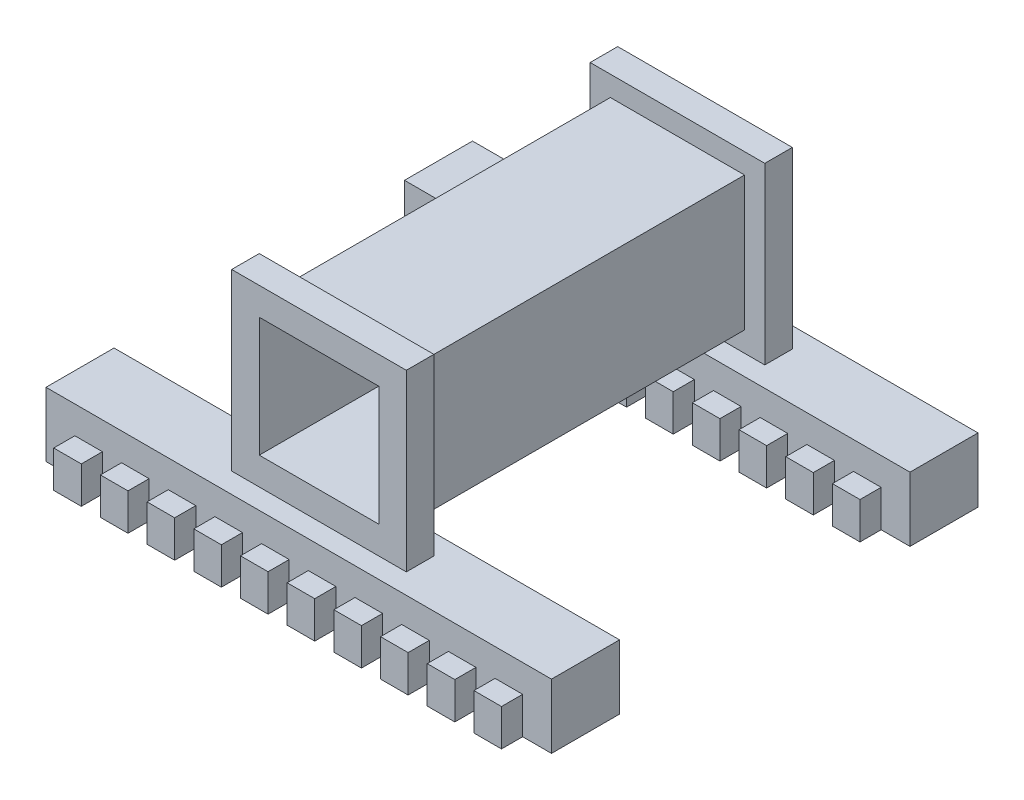
SolidWorks part; units mm, degrees
ref_plane "前视基准面" through (0, 0, 0) normal (0, 0, 1) x (1, 0, 0)
ref_plane "上视基准面" through (0, 0, 0) normal (0, 1, 0) x (1, 0, 0)
ref_plane "右视基准面" through (0, 0, 0) normal (1, 0, 0) x (0, 0, -1)
sketch "草图1" plane through (0, 0, 0) normal (0, 0, 1) x (1, 0, 0)
  line L0 (-9.5, 9.5) -> (9.5, 9.5)
  line L1 (-6.5, -6.5) -> (6.5, -6.5)
  line L2 (-6.5, -6.5) -> (-6.5, 6.5)
  line L3 (-6.5, 6.5) -> (6.5, 6.5)
  line L4 (6.5, -6.5) -> (6.5, 6.5)
  line L5 (-6.5, -6.5) -> (6.5, 6.5) construction
  line L6 (-6.5, 6.5) -> (6.5, -6.5) construction
  line L7 (9.5, -9.5) -> (9.5, 9.5)
  line L8 (-9.5, -9.5) -> (9.5, -9.5)
  line L9 (-9.5, -9.5) -> (-9.5, 9.5)
  line L10 (-7.3, 7.3) -> (7.3, 7.3)
  line L11 (7.3, -7.3) -> (7.3, 7.3)
  line L12 (-7.3, -7.3) -> (7.3, -7.3)
  line L13 (-7.3, -7.3) -> (-7.3, 7.3)
  line L15 (-27.5, -9.5) -> (27.5, -9.5)
  line L16 (-27.5, -9.5) -> (-27.5, -16.5)
  line L17 (-27.5, -16.5) -> (27.5, -16.5)
  line L18 (27.5, -9.5) -> (27.5, -16.5)
  point P0 (0, 0)
  dimension "D1" = 3
  dimension "D2" = 0.8
extrude "凸台-拉伸1" add sketch "草图1" along normal mid plane 42 contours L18 L15 L8 L16 L17 | L9 L8 L7 L0 L12 L13 L10 L11 | L13 L10 L11 L12 region at (0, 9.2313, 0) region at (0, -13, 0)
extrude "切除-拉伸1" cut sketch "草图1<3>" against normal mid plane 42 contours L2 L3 L4 L1
sketch "草图1<3>" plane through (0, 0, 0) normal (0, 0, 1) x (1, 0, 0) same geometry as "草图1"
sketch "草图2" plane through (0, 0, 0) normal (1, 0, 0) x (0, 0, -1)
  line L0 (21, -16.5) -> (21, -9.5) construction
  line L1 (21, -9.5) -> (-21, -9.5) construction
  line L2 (-21, -9.5) -> (-21, -16.5) construction
  line L3 (-21, -16.5) -> (21, -16.5) construction
  line L4 (21, -9.5) -> (21, 9.5) construction
  line L5 (21, 9.5) -> (-21, 9.5) construction
  line L6 (-21, 9.5) -> (-21, -9.5) construction
  line L7 (-21, -9.5) -> (21, -9.5) construction
  line L8 (21, -16.5) -> (21, -9.5)
  line L9 (21, -9.5) -> (-21, -9.5)
  line L10 (-21, -9.5) -> (-21, -16.5)
  line L11 (-21, -16.5) -> (21, -16.5)
  line L12 (21, -9.5) -> (21, 9.5)
  line L13 (21, 9.5) -> (-21, 9.5)
  line L14 (-21, 9.5) -> (-21, -9.5)
  line L15 (-21, -9.5) -> (21, -9.5)
extrude "切除-拉伸6" cut sketch "草图1<12>" against normal mid plane 36 contours L1 L4 L3 L2 | L9 L0 L7 L8 | L13 L10 L11 L12 region at (0, 0, 0)
sketch "草图1<12>" plane through (0, 0, 0) normal (0, 0, 1) x (1, 0, 0) same geometry as "草图1"
extrude "切除-拉伸7" cut sketch "草图1<13>" against normal mid plane 29 contours L18 L15 L8 L16 L17 region at (0, -13, 0)
sketch "草图1<13>" plane through (0, 0, 0) normal (0, 0, 1) x (1, 0, 0) same geometry as "草图1"
sketch "草图4" plane through (0, 0, 0) normal (1, 0, 0) x (0, 0, -1)
  line L0 (-21, -9.5) -> (-14.5, -9.5) construction
  line L1 (-14.5, -9.5) -> (-14.5, -16.5) construction
  line L2 (-14.5, -16.5) -> (-21, -16.5) construction
  line L3 (-21, -16.5) -> (-21, -9.5) construction
  line L4 (-18, 9.5) -> (-18, -9.5) construction
  line L5 (-18, -9.5) -> (-21, -9.5) construction
  line L6 (-21, -9.5) -> (-21, 9.5) construction
  line L7 (-21, 9.5) -> (-18, 9.5) construction
  line L8 (-18, -7.3) -> (-18, 7.3) construction
  line L9 (-18, 7.3) -> (18, 7.3) construction
  line L10 (18, 7.3) -> (18, -7.3) construction
  line L11 (18, -7.3) -> (-18, -7.3) construction
  line L12 (21, -9.5) -> (18, -9.5) construction
  line L13 (18, -9.5) -> (18, 9.5) construction
  line L14 (18, 9.5) -> (21, 9.5) construction
  line L15 (21, 9.5) -> (21, -9.5) construction
  line L16 (14.5, -16.5) -> (14.5, -9.5) construction
  line L17 (14.5, -9.5) -> (21, -9.5) construction
  line L18 (21, -9.5) -> (21, -16.5) construction
  line L19 (21, -16.5) -> (14.5, -16.5) construction
  line L20 (-21, -9.5) -> (-14.5, -9.5)
  line L21 (-14.5, -9.5) -> (-14.5, -16.5)
  line L22 (-14.5, -16.5) -> (-21, -16.5)
  line L23 (-21, -16.5) -> (-21, -9.5)
  line L24 (-18, 9.5) -> (-18, -9.5)
  line L25 (-18, -9.5) -> (-21, -9.5)
  line L26 (-21, -9.5) -> (-21, 9.5)
  line L27 (-21, 9.5) -> (-18, 9.5)
  line L28 (-18, -7.3) -> (-18, 7.3)
  line L29 (-18, 7.3) -> (18, 7.3)
  line L30 (18, 7.3) -> (18, -7.3)
  line L31 (18, -7.3) -> (-18, -7.3)
  line L32 (21, -9.5) -> (18, -9.5)
  line L33 (18, -9.5) -> (18, 9.5)
  line L34 (18, 9.5) -> (21, 9.5)
  line L35 (21, 9.5) -> (21, -9.5)
  line L36 (14.5, -16.5) -> (14.5, -9.5)
  line L37 (14.5, -9.5) -> (21, -9.5)
  line L38 (21, -9.5) -> (21, -16.5)
  line L39 (21, -16.5) -> (14.5, -16.5)
  line L40 (21, -9.5) -> (24.5, -9.5)
  line L41 (24.5, -9.5) -> (24.5, -16.5)
  line L42 (24.5, -16.5) -> (21, -16.5)
  line L43 (-21, -16.5) -> (-24.5049, -16.5)
  line L44 (-24.5049, -16.5) -> (-24.5049, -9.5)
  line L45 (-24.5049, -9.5) -> (-21, -9.5)
extrude "凸台-拉伸2" add sketch "草图4" along normal mid plane 55 contours L42 L41 L40 L38 | L45 L44 L43 L23 region at (0, -13, 22.7525) region at (0, -13, -22.75)
sketch "草图5" plane through (0, 0, -24.5) normal (0, 0, -1) x (-1, 0, 0)
  line L4 (27.5, -16.5) -> (27.5, -9.5)
  line L5 (27.5, -9.5) -> (-27.5, -9.5)
  line L6 (-27.5, -9.5) -> (-27.5, -16.5)
  line L7 (-27.5, -16.5) -> (27.5, -16.5)
  line L8 (27.5, -16.5) -> (27.5, -9.5)
  line L9 (27.5, -9.5) -> (-27.5, -9.5)
  line L10 (-27.5, -9.5) -> (-27.5, -16.5)
  line L12 (-9.5, -9.5) -> (9.5, -9.5)
  line L13 (-9.5, 9.5) -> (-9.5, -9.5)
  line L14 (9.5, 9.5) -> (-9.5, 9.5)
  line L15 (9.5, -9.5) -> (9.5, 9.5)
  line L16 (-9.5, -9.5) -> (9.5, -9.5)
  line L17 (-9.5, 9.5) -> (-9.5, -9.5)
  line L18 (9.5, 9.5) -> (-9.5, 9.5)
  line L19 (9.5, -9.5) -> (9.5, 9.5)
  line L24 (-27.5, -16.5) -> (27.5, -16.5) construction
  line L37 (22.8593, -16.5) -> (27.5, -16.5)
  line L50 (-21.36, -16.5) -> (-24.36, -16.5)
  line L55 (-11.187, -12.5036) -> (-14.213, -12.5036)
  line L56 (-11.187, -12.5036) -> (-11.187, -16.5)
  line L61 (-6.12, -16.5) -> (-9.12, -16.5)
  line L62 (-6.12, -16.5) -> (-6.12, -12.5036)
  line L68 (-1.04, -16.4978) -> (-4.04, -16.4978)
  line L86 (9.12, -16.5) -> (6.12, -16.5)
  line L91 (9.12, -16.5) -> (9.12, -12.5)
  line L92 (9.12, -12.5) -> (6.12, -12.5)
  line L97 (6.12, -16.5) -> (6.12, -12.5)
  line L98 (9.12, -16.5) -> (6.12, -12.5) construction
  line L103 (-21.36, -16.5) -> (-21.36, -12.5036)
  line L104 (-21.36, -12.5036) -> (-24.36, -12.5036)
  line L105 (-24.36, -16.5) -> (-24.36, -12.5036)
  line L106 (-21.36, -16.5) -> (-24.36, -12.5036) construction
  line L107 (-21.36, -12.5036) -> (-24.36, -16.5) construction
  line L108 (-19.28, -16.5) -> (-16.28, -16.5)
  line L109 (-19.28, -16.5) -> (-19.28, -12.5036)
  line L110 (-19.28, -12.5036) -> (-16.28, -12.5036)
  line L111 (-16.28, -16.5) -> (-16.28, -12.5036)
  line L112 (-19.28, -16.5) -> (-16.28, -12.5036) construction
  line L113 (-19.28, -12.5036) -> (-16.28, -16.5) construction
  line L114 (-11.187, -16.5) -> (-14.213, -16.5)
  line L115 (-14.213, -12.5036) -> (-14.213, -16.5)
  line L116 (-11.187, -12.5036) -> (-14.213, -16.5) construction
  line L117 (-11.187, -16.5) -> (-14.213, -12.5036) construction
  line L118 (-6.12, -12.5036) -> (-9.12, -12.5036)
  line L119 (-9.12, -16.5) -> (-9.12, -12.5036)
  line L120 (-6.12, -16.5) -> (-9.12, -12.5036) construction
  line L121 (-6.12, -12.5036) -> (-9.12, -16.5) construction
  line L122 (-1.04, -16.4978) -> (-1.04, -12.4978)
  line L123 (-1.04, -12.4978) -> (-4.04, -12.4978)
  line L124 (-4.04, -16.4978) -> (-4.04, -12.4978)
  line L125 (-1.04, -16.4978) -> (-4.04, -12.4978) construction
  line L126 (-1.04, -12.4978) -> (-4.04, -16.4978) construction
  line L128 (9.12, -12.5) -> (6.12, -16.5) construction
  line L129 (4.04, -16.5) -> (1.038, -16.5)
  line L130 (4.04, -16.5) -> (4.04, -12.4956)
  line L131 (4.04, -12.4956) -> (1.038, -12.4956)
  line L132 (1.038, -16.5) -> (1.038, -12.4956)
  line L133 (4.04, -16.5) -> (1.038, -12.4956) construction
  line L134 (4.04, -12.4956) -> (1.038, -16.5) construction
  line L135 (14.2014, -16.5) -> (11.1986, -16.5)
  line L136 (14.2014, -16.5) -> (14.2014, -12.5)
  line L137 (14.2014, -12.5) -> (11.1986, -12.5)
  line L138 (11.1986, -16.5) -> (11.1986, -12.5)
  line L139 (14.2014, -16.5) -> (11.1986, -12.5) construction
  line L140 (14.2014, -12.5) -> (11.1986, -16.5) construction
  line L141 (19.28, -16.4935) -> (16.28, -16.4935)
  line L142 (19.28, -16.4935) -> (19.28, -12.4935)
  line L143 (19.28, -12.4935) -> (16.28, -12.4935)
  line L144 (16.28, -16.4935) -> (16.28, -12.4935)
  line L145 (19.28, -16.4935) -> (16.28, -12.4935) construction
  line L146 (19.28, -12.4935) -> (16.28, -16.4935) construction
  line L151 (24.3586, -16.5) -> (21.36, -16.5)
  line L152 (24.3586, -16.5) -> (24.3586, -12.487)
  line L153 (24.3586, -12.487) -> (21.36, -12.487)
  line L154 (21.36, -16.5) -> (21.36, -12.487)
  line L155 (24.3586, -16.5) -> (21.36, -12.487) construction
  line L156 (24.3586, -12.487) -> (21.36, -16.5) construction
  point P6 (-22.86, -14.5018)
  point P11 (0, 0)
  point P33 (-17.78, -14.5018)
  point P35 (-17.78, -14.5018)
  point P39 (-12.7, -14.5018)
  point P40 (-12.7, -14.5018)
  point P45 (-7.62, -14.5018)
  point P50 (-2.54, -14.4978)
  point P55 (2.539, -14.4978)
  point P60 (7.62, -14.5)
  point P65 (12.7, -14.5)
  point P70 (17.78, -14.4935)
  point P75 (22.8593, -14.4935)
  dimension "D1" = 0
  dimension "D2" = 0
sketch "草图10" plane through (27.5, 0, 0) normal (1, 0, 0) x (0, 0, -1)
  line L0 (-24.5049, -16.5) -> (-25.5049, -16.5)
  line L1 (-24.5049, -16.5) -> (-24.5049, -9.5)
  line L2 (-24.5049, -9.5) -> (-25.5049, -9.5)
  line L3 (-25.5049, -9.5) -> (-25.5049, -16.5)
  line L4 (-14.5, -16.5) -> (-13.5, -16.5)
  line L5 (-13.5, -16.5) -> (-13.5, -9.5)
  line L6 (-13.5, -9.5) -> (-14.5, -9.5)
  line L7 (-14.5, -9.5) -> (-14.5, -16.5)
  line L8 (14.4975, -9.5) -> (14.4975, -16.5)
  line L11 (-0.0012, -16.5) -> (-0.0012, -9.5)
  line L12 (13.4975, -9.5) -> (14.4975, -9.5)
  line L13 (13.4975, -16.5) -> (13.4975, -9.5)
  line L14 (14.4975, -16.5) -> (13.4975, -16.5)
  line L15 (25.5025, -9.5) -> (25.5025, -16.5)
  line L16 (24.5025, -9.5) -> (25.5025, -9.5)
  line L17 (24.5025, -16.5) -> (24.5025, -9.5)
  line L18 (24.5025, -16.5) -> (25.5025, -16.5)
extrude "凸台-拉伸4" add sketch "草图10" against normal blind 55 contours L7 L4 L5 L6 | L3 L0 L1 L2
sketch "草图14" plane through (27.5, 0, 0) normal (1, 0, 0) x (0, 0, -1)
  line L0 (14.5, -9.5) -> (13.5, -9.5)
  line L1 (14.5, -16.5) -> (13.5, -16.5)
  line L2 (13.5, -16.5) -> (13.5, -9.5)
  line L3 (24.5, -9.5) -> (25.5, -9.5)
  line L4 (24.5, -16.5) -> (25.5, -16.5)
  line L5 (25.5, -16.5) -> (25.5, -9.5)
  line L6 (24.5, -9.5) -> (24.5, -16.5)
  line L7 (14.5, -9.5) -> (14.5, -16.5)
extrude "凸台-拉伸6" add sketch "草图14" against normal blind 55
sketch "草图15" plane through (0, 0, -25.5) normal (0, 0, -1) x (-1, 0, 0)
  line L0 (-27.5, -16.5) -> (-22.86, -16.5)
  line L1 (27.5, -16.5) -> (-27.5, -16.5) construction
  line L2 (-22.86, -16.5) -> (-22.86, -12.5)
  line L4 (-17.78, -12.5) -> (-17.78, -16.5)
  line L5 (-11.2, -16.5) -> (-14.2, -16.5)
  line L6 (-12.7, -16.5) -> (-12.7, -12.5)
  line L7 (-11.2, -16.5) -> (-11.2, -12.5)
  line L8 (-7.62, -12.5) -> (-7.62, -16.5)
  line L9 (-11.2, -12.5) -> (-14.2, -12.5)
  line L10 (-2.54, -16.5) -> (-2.54, -12.5)
  line L11 (-1.04, -16.5) -> (-4.04, -16.5)
  line L12 (2.54, -12.5) -> (2.54, -16.5)
  line L13 (-1.04, -16.5) -> (-1.04, -12.5)
  line L14 (7.62, -16.5) -> (7.62, -12.5)
  line L15 (6.12, -16.5) -> (9.12, -16.5)
  line L16 (12.7, -12.5) -> (12.7, -16.5)
  line L17 (6.12, -16.5) -> (6.12, -12.5)
  line L18 (17.78, -16.5) -> (17.78, -12.5)
  line L19 (6.12, -12.5) -> (9.12, -12.5)
  line L20 (22.86, -12.5) -> (22.86, -16.5)
  line L21 (24.36, -16.5) -> (21.36, -16.5)
  line L31 (24.36, -16.5) -> (24.36, -12.5)
  line L32 (24.36, -12.5) -> (21.36, -12.5)
  line L37 (9.12, -16.5) -> (9.12, -12.5)
  line L38 (6.12, -16.5) -> (9.12, -12.5) construction
  line L39 (-19.28, -16.5) -> (-16.28, -16.5)
  line L48 (-21.36, -16.5) -> (-24.36, -16.5)
  line L49 (-21.36, -16.5) -> (-21.36, -12.5)
  line L50 (-21.36, -12.5) -> (-24.36, -12.5)
  line L51 (-24.36, -16.5) -> (-24.36, -12.5)
  line L52 (-21.36, -16.5) -> (-24.36, -12.5) construction
  line L53 (-21.36, -12.5) -> (-24.36, -16.5) construction
  line L58 (-19.28, -16.5) -> (-19.28, -12.5)
  line L59 (-19.28, -12.5) -> (-16.28, -12.5)
  line L60 (-16.28, -16.5) -> (-16.28, -12.5)
  line L61 (-19.28, -16.5) -> (-16.28, -12.5) construction
  line L62 (-19.28, -12.5) -> (-16.28, -16.5) construction
  line L67 (-14.2, -16.5) -> (-14.2, -12.5)
  line L68 (-11.2, -16.5) -> (-14.2, -12.5) construction
  line L69 (-11.2, -12.5) -> (-14.2, -16.5) construction
  line L70 (-9.12, -16.5) -> (-6.12, -16.5)
  line L71 (-9.12, -16.5) -> (-9.12, -12.5)
  line L72 (-9.12, -12.5) -> (-6.12, -12.5)
  line L73 (-6.12, -16.5) -> (-6.12, -12.5)
  line L74 (-9.12, -16.5) -> (-6.12, -12.5) construction
  line L75 (-9.12, -12.5) -> (-6.12, -16.5) construction
  line L76 (-1.04, -12.5) -> (-4.04, -12.5)
  line L77 (-4.04, -16.5) -> (-4.04, -12.5)
  line L78 (-1.04, -16.5) -> (-4.04, -12.5) construction
  line L79 (-1.04, -12.5) -> (-4.04, -16.5) construction
  line L80 (4.04, -16.5) -> (1.04, -16.5)
  line L81 (4.04, -16.5) -> (4.04, -12.5)
  line L82 (4.04, -12.5) -> (1.04, -12.5)
  line L83 (1.04, -16.5) -> (1.04, -12.5)
  line L84 (4.04, -16.5) -> (1.04, -12.5) construction
  line L85 (4.04, -12.5) -> (1.04, -16.5) construction
  line L86 (6.12, -12.5) -> (9.12, -16.5) construction
  line L87 (11.2, -16.5) -> (14.2, -16.5)
  line L88 (11.2, -16.5) -> (11.2, -12.5)
  line L89 (11.2, -12.5) -> (14.2, -12.5)
  line L90 (14.2, -16.5) -> (14.2, -12.5)
  line L91 (11.2, -16.5) -> (14.2, -12.5) construction
  line L92 (11.2, -12.5) -> (14.2, -16.5) construction
  line L93 (16.28, -16.5) -> (19.28, -16.5)
  line L94 (16.28, -16.5) -> (16.28, -12.5)
  line L95 (16.28, -12.5) -> (19.28, -12.5)
  line L96 (19.28, -16.5) -> (19.28, -12.5)
  line L97 (16.28, -16.5) -> (19.28, -12.5) construction
  line L98 (16.28, -12.5) -> (19.28, -16.5) construction
  line L99 (21.36, -16.5) -> (21.36, -12.5)
  line L100 (24.36, -16.5) -> (21.36, -12.5) construction
  line L101 (24.36, -12.5) -> (21.36, -16.5) construction
  point P17 (22.86, -14.5)
  point P25 (22.86, -14.5)
  point P26 (22.86, -14.5)
  point P31 (17.78, -14.5)
  point P32 (7.62, -14.5)
  point P36 (-22.86, -14.5)
  point P41 (-17.78, -14.5)
  point P42 (-17.78, -14.5)
  point P47 (-12.7, -14.5)
  point P52 (-7.62, -14.5)
  point P57 (-2.54, -14.5)
  point P62 (2.54, -14.5)
  point P68 (12.7, -14.5)
  point P73 (17.78, -14.5)
  point P78 (0, 0)
  point P79 (0, 0)
  line M64 (-27.5, -9.5) -> (-27.5, -16.5)
  line M65 (-27.5, -16.5) -> (27.5, -16.5)
  line M66 (27.5, -16.5) -> (27.5, -9.5)
  line M67 (27.5, -9.5) -> (-27.5, -9.5)
extrude "切除-拉伸17" cut sketch "草图15" against normal blind 2.3 contours L99 L32 L31 L51 L50 L49 L58 L59 L60 L67 L9 L7 L71 L72 L73 L77 L76 L13 L83 L82 L81 L17 L19 L37 L88 L89 L90 L94 M65 M66 M67 M64 region at (0, -12.3208, -25.5)
sketch "草图16" plane through (0, 0, 13.5) normal (0, 0, -1) x (-1, 0, 0)
  line L0 (21.36, -16.5) -> (24.36, -16.5) construction
  line L1 (24.36, -16.5) -> (24.36, -12.5) construction
  line L2 (24.36, -12.5) -> (21.36, -12.5) construction
  line L3 (21.36, -12.5) -> (21.36, -16.5) construction
  line L4 (-27.5, -9.5) -> (-27.5, -16.5)
  line L5 (-27.5, -16.5) -> (27.5, -16.5)
  line L6 (27.5, -16.5) -> (27.5, -9.5)
  line L7 (27.5, -9.5) -> (-27.5, -9.5)
  line L8 (-27.5, -9.5) -> (-27.5, -16.5)
  line L9 (-27.5, -16.5) -> (27.5, -16.5)
  line L10 (27.5, -16.5) -> (27.5, -9.5)
  line L11 (27.5, -9.5) -> (-27.5, -9.5)
  line L12 (16.28, -16.5) -> (19.28, -16.5) construction
  line L13 (19.28, -16.5) -> (19.28, -12.5) construction
  line L14 (19.28, -12.5) -> (16.28, -12.5) construction
  line L15 (16.28, -12.5) -> (16.28, -16.5) construction
  line L16 (11.2, -16.5) -> (14.2, -16.5) construction
  line L17 (14.2, -16.5) -> (14.2, -12.5) construction
  line L18 (14.2, -12.5) -> (11.2, -12.5) construction
  line L19 (11.2, -12.5) -> (11.2, -16.5) construction
  line L20 (6.12, -16.5) -> (9.12, -16.5) construction
  line L21 (9.12, -16.5) -> (9.12, -12.5) construction
  line L22 (9.12, -12.5) -> (6.12, -12.5) construction
  line L23 (6.12, -12.5) -> (6.12, -16.5) construction
  line L24 (1.04, -16.5) -> (4.04, -16.5) construction
  line L25 (4.04, -16.5) -> (4.04, -12.5) construction
  line L26 (4.04, -12.5) -> (1.04, -12.5) construction
  line L27 (1.04, -12.5) -> (1.04, -16.5) construction
  line L28 (-4.04, -16.5) -> (-1.04, -16.5) construction
  line L29 (-1.04, -16.5) -> (-1.04, -12.5) construction
  line L30 (-1.04, -12.5) -> (-4.04, -12.5) construction
  line L31 (-4.04, -12.5) -> (-4.04, -16.5) construction
  line L32 (-9.12, -16.5) -> (-6.12, -16.5) construction
  line L33 (-6.12, -16.5) -> (-6.12, -12.5) construction
  line L34 (-6.12, -12.5) -> (-9.12, -12.5) construction
  line L35 (-9.12, -12.5) -> (-9.12, -16.5) construction
  line L36 (-14.2, -16.5) -> (-11.2, -16.5) construction
  line L37 (-11.2, -16.5) -> (-11.2, -12.5) construction
  line L38 (-11.2, -12.5) -> (-14.2, -12.5) construction
  line L39 (-14.2, -12.5) -> (-14.2, -16.5) construction
  line L40 (-19.28, -16.5) -> (-16.28, -16.5) construction
  line L41 (-16.28, -16.5) -> (-16.28, -12.5) construction
  line L42 (-16.28, -12.5) -> (-19.28, -12.5) construction
  line L43 (-19.28, -12.5) -> (-19.28, -16.5) construction
  line L44 (-24.36, -16.5) -> (-21.36, -16.5) construction
  line L45 (-21.36, -16.5) -> (-21.36, -12.5) construction
  line L46 (-21.36, -12.5) -> (-24.36, -12.5) construction
  line L47 (-24.36, -12.5) -> (-24.36, -16.5) construction
  line L48 (21.36, -16.5) -> (24.36, -16.5)
  line L49 (24.36, -16.5) -> (24.36, -12.5)
  line L50 (24.36, -12.5) -> (21.36, -12.5)
  line L51 (21.36, -12.5) -> (21.36, -16.5)
  line L52 (16.28, -16.5) -> (19.28, -16.5)
  line L53 (19.28, -16.5) -> (19.28, -12.5)
  line L54 (19.28, -12.5) -> (16.28, -12.5)
  line L55 (16.28, -12.5) -> (16.28, -16.5)
  line L56 (11.2, -16.5) -> (14.2, -16.5)
  line L57 (14.2, -16.5) -> (14.2, -12.5)
  line L58 (14.2, -12.5) -> (11.2, -12.5)
  line L59 (11.2, -12.5) -> (11.2, -16.5)
  line L60 (6.12, -16.5) -> (9.12, -16.5)
  line L61 (9.12, -16.5) -> (9.12, -12.5)
  line L62 (9.12, -12.5) -> (6.12, -12.5)
  line L63 (6.12, -12.5) -> (6.12, -16.5)
  line L64 (1.04, -16.5) -> (4.04, -16.5)
  line L65 (4.04, -16.5) -> (4.04, -12.5)
  line L66 (4.04, -12.5) -> (1.04, -12.5)
  line L67 (1.04, -12.5) -> (1.04, -16.5)
  line L68 (-4.04, -16.5) -> (-1.04, -16.5)
  line L69 (-1.04, -16.5) -> (-1.04, -12.5)
  line L70 (-1.04, -12.5) -> (-4.04, -12.5)
  line L71 (-4.04, -12.5) -> (-4.04, -16.5)
  line L72 (-9.12, -16.5) -> (-6.12, -16.5)
  line L73 (-6.12, -16.5) -> (-6.12, -12.5)
  line L74 (-6.12, -12.5) -> (-9.12, -12.5)
  line L75 (-9.12, -12.5) -> (-9.12, -16.5)
  line L76 (-14.2, -16.5) -> (-11.2, -16.5)
  line L77 (-11.2, -16.5) -> (-11.2, -12.5)
  line L78 (-11.2, -12.5) -> (-14.2, -12.5)
  line L79 (-14.2, -12.5) -> (-14.2, -16.5)
  line L80 (-19.28, -16.5) -> (-16.28, -16.5)
  line L81 (-16.28, -16.5) -> (-16.28, -12.5)
  line L82 (-16.28, -12.5) -> (-19.28, -12.5)
  line L83 (-19.28, -12.5) -> (-19.28, -16.5)
  line L84 (-24.36, -16.5) -> (-21.36, -16.5)
  line L85 (-21.36, -16.5) -> (-21.36, -12.5)
  line L86 (-21.36, -12.5) -> (-24.36, -12.5)
  line L87 (-24.36, -12.5) -> (-24.36, -16.5)
  line M5 (-27.5, -9.5) -> (-27.5, -16.5)
  line M6 (-27.5, -16.5) -> (27.5, -16.5)
  line M7 (27.5, -16.5) -> (27.5, -9.5)
  line M8 (27.5, -9.5) -> (-27.5, -9.5)
  dimension "D1" = 0
extrude "切除-拉伸18" cut sketch "草图16" against normal blind 2.3 contours L87 L86 L85 L83 L82 L81 L79 L78 L77 L75 L74 L73 L71 L70 L69 L67 L66 L65 L63 L62 L61 L59 L58 L57 L55 L54 L53 L51 L50 L49 M6 M7 M8 M5 region at (0, -12.3208, 13.5)
sketch "草图17" plane through (0, 0, -13.5) normal (0, 0, 1) x (1, 0, 0)
  line L0 (-21.36, -16.5) -> (-24.36, -16.5) construction
  line L1 (-24.36, -16.5) -> (-24.36, -12.5) construction
  line L2 (-24.36, -12.5) -> (-21.36, -12.5) construction
  line L3 (-21.36, -12.5) -> (-21.36, -16.5) construction
  line L4 (27.5, -16.5) -> (27.5, -9.5)
  line L5 (27.5, -9.5) -> (-27.5, -9.5)
  line L6 (-27.5, -9.5) -> (-27.5, -16.5)
  line L7 (-27.5, -16.5) -> (27.5, -16.5)
  line L8 (27.5, -16.5) -> (27.5, -9.5)
  line L9 (27.5, -9.5) -> (-27.5, -9.5)
  line L10 (-27.5, -9.5) -> (-27.5, -16.5)
  line L11 (-27.5, -16.5) -> (27.5, -16.5)
  line L12 (-16.28, -16.5) -> (-19.28, -16.5) construction
  line L13 (-19.28, -16.5) -> (-19.28, -12.5) construction
  line L14 (-19.28, -12.5) -> (-16.28, -12.5) construction
  line L15 (-16.28, -12.5) -> (-16.28, -16.5) construction
  line L16 (-11.2, -16.5) -> (-14.2, -16.5) construction
  line L17 (-14.2, -16.5) -> (-14.2, -12.5) construction
  line L18 (-14.2, -12.5) -> (-11.2, -12.5) construction
  line L19 (-11.2, -12.5) -> (-11.2, -16.5) construction
  line L20 (-6.12, -16.5) -> (-9.12, -16.5) construction
  line L21 (-9.12, -16.5) -> (-9.12, -12.5) construction
  line L22 (-9.12, -12.5) -> (-6.12, -12.5) construction
  line L23 (-6.12, -12.5) -> (-6.12, -16.5) construction
  line L24 (-1.04, -16.5) -> (-4.04, -16.5) construction
  line L25 (-4.04, -16.5) -> (-4.04, -12.5) construction
  line L26 (-4.04, -12.5) -> (-1.04, -12.5) construction
  line L27 (-1.04, -12.5) -> (-1.04, -16.5) construction
  line L28 (4.04, -16.5) -> (1.04, -16.5) construction
  line L29 (1.04, -16.5) -> (1.04, -12.5) construction
  line L30 (1.04, -12.5) -> (4.04, -12.5) construction
  line L31 (4.04, -12.5) -> (4.04, -16.5) construction
  line L32 (9.12, -16.5) -> (6.12, -16.5) construction
  line L33 (6.12, -16.5) -> (6.12, -12.5) construction
  line L34 (6.12, -12.5) -> (9.12, -12.5) construction
  line L35 (9.12, -12.5) -> (9.12, -16.5) construction
  line L36 (14.2, -16.5) -> (11.2, -16.5) construction
  line L37 (11.2, -16.5) -> (11.2, -12.5) construction
  line L38 (11.2, -12.5) -> (14.2, -12.5) construction
  line L39 (14.2, -12.5) -> (14.2, -16.5) construction
  line L40 (19.28, -16.5) -> (16.28, -16.5) construction
  line L41 (16.28, -16.5) -> (16.28, -12.5) construction
  line L42 (16.28, -12.5) -> (19.28, -12.5) construction
  line L43 (19.28, -12.5) -> (19.28, -16.5) construction
  line L44 (21.36, -12.5) -> (24.36, -12.5) construction
  line L45 (24.36, -12.5) -> (24.36, -16.5) construction
  line L46 (24.36, -16.5) -> (21.36, -16.5) construction
  line L47 (21.36, -16.5) -> (21.36, -12.5) construction
  line L48 (-21.36, -16.5) -> (-24.36, -16.5)
  line L49 (-24.36, -16.5) -> (-24.36, -12.5)
  line L50 (-24.36, -12.5) -> (-21.36, -12.5)
  line L51 (-21.36, -12.5) -> (-21.36, -16.5)
  line L52 (-16.28, -16.5) -> (-19.28, -16.5)
  line L53 (-19.28, -16.5) -> (-19.28, -12.5)
  line L54 (-19.28, -12.5) -> (-16.28, -12.5)
  line L55 (-16.28, -12.5) -> (-16.28, -16.5)
  line L56 (-11.2, -16.5) -> (-14.2, -16.5)
  line L57 (-14.2, -16.5) -> (-14.2, -12.5)
  line L58 (-14.2, -12.5) -> (-11.2, -12.5)
  line L59 (-11.2, -12.5) -> (-11.2, -16.5)
  line L60 (-6.12, -16.5) -> (-9.12, -16.5)
  line L61 (-9.12, -16.5) -> (-9.12, -12.5)
  line L62 (-9.12, -12.5) -> (-6.12, -12.5)
  line L63 (-6.12, -12.5) -> (-6.12, -16.5)
  line L64 (-1.04, -16.5) -> (-4.04, -16.5)
  line L65 (-4.04, -16.5) -> (-4.04, -12.5)
  line L66 (-4.04, -12.5) -> (-1.04, -12.5)
  line L67 (-1.04, -12.5) -> (-1.04, -16.5)
  line L68 (4.04, -16.5) -> (1.04, -16.5)
  line L69 (1.04, -16.5) -> (1.04, -12.5)
  line L70 (1.04, -12.5) -> (4.04, -12.5)
  line L71 (4.04, -12.5) -> (4.04, -16.5)
  line L72 (9.12, -16.5) -> (6.12, -16.5)
  line L73 (6.12, -16.5) -> (6.12, -12.5)
  line L74 (6.12, -12.5) -> (9.12, -12.5)
  line L75 (9.12, -12.5) -> (9.12, -16.5)
  line L76 (14.2, -16.5) -> (11.2, -16.5)
  line L77 (11.2, -16.5) -> (11.2, -12.5)
  line L78 (11.2, -12.5) -> (14.2, -12.5)
  line L79 (14.2, -12.5) -> (14.2, -16.5)
  line L80 (19.28, -16.5) -> (16.28, -16.5)
  line L81 (16.28, -16.5) -> (16.28, -12.5)
  line L82 (16.28, -12.5) -> (19.28, -12.5)
  line L83 (19.28, -12.5) -> (19.28, -16.5)
  line L84 (21.36, -12.5) -> (24.36, -12.5)
  line L85 (24.36, -12.5) -> (24.36, -16.5)
  line L86 (24.36, -16.5) -> (21.36, -16.5)
  line L87 (21.36, -16.5) -> (21.36, -12.5)
  line M5 (27.5, -16.5) -> (27.5, -9.5)
  line M6 (27.5, -9.5) -> (-27.5, -9.5)
  line M7 (-27.5, -9.5) -> (-27.5, -16.5)
  line M8 (-27.5, -16.5) -> (27.5, -16.5)
  dimension "D1" = 0
extrude "切除-拉伸19" cut sketch "草图17" against normal blind 2.3 contours L87 L84 L85 L11 L49 L50 L51 L53 L54 L55 L57 L58 L59 L61 L62 L63 L65 L66 L67 L69 L70 L71 L73 L74 L75 L77 L78 L79 L81 L82 L83 M8 M5 M6 M7 region at (0, -12.3208, -13.5)
sketch "草图18" plane through (0, 0, 25.5049) normal (0, 0, 1) x (1, 0, 0)
  line L0 (24.36, -16.5) -> (24.36, -12.5) construction
  line L1 (24.36, -12.5) -> (21.36, -12.5) construction
  line L2 (21.36, -12.5) -> (21.36, -16.5) construction
  line L3 (21.36, -16.5) -> (24.36, -16.5) construction
  line L4 (27.5, -16.5) -> (27.5, -9.5)
  line L5 (27.5, -9.5) -> (-27.5, -9.5)
  line L6 (-27.5, -9.5) -> (-27.5, -16.5)
  line L7 (-27.5, -16.5) -> (27.5, -16.5)
  line L8 (27.5, -16.5) -> (27.5, -9.5)
  line L9 (27.5, -9.5) -> (-27.5, -9.5)
  line L10 (-27.5, -9.5) -> (-27.5, -16.5)
  line L11 (-27.5, -16.5) -> (27.5, -16.5)
  line L12 (-16.28, -16.5) -> (-16.28, -12.5)
  line L13 (-16.28, -12.5) -> (-19.28, -12.5)
  line L14 (-19.28, -12.5) -> (-19.28, -16.5)
  line L15 (-19.28, -16.5) -> (-16.28, -16.5)
  line L16 (-16.28, -16.5) -> (-16.28, -12.5)
  line L17 (-16.28, -12.5) -> (-19.28, -12.5)
  line L18 (-19.28, -12.5) -> (-19.28, -16.5)
  line L19 (-19.28, -16.5) -> (-16.28, -16.5)
  line L20 (19.28, -16.5) -> (19.28, -12.5) construction
  line L21 (19.28, -12.5) -> (16.28, -12.5) construction
  line L22 (16.28, -12.5) -> (16.28, -16.5) construction
  line L23 (16.28, -16.5) -> (19.28, -16.5) construction
  line L24 (14.2, -16.5) -> (14.2, -12.5) construction
  line L25 (14.2, -12.5) -> (11.2, -12.5) construction
  line L26 (11.2, -12.5) -> (11.2, -16.5) construction
  line L27 (11.2, -16.5) -> (14.2, -16.5) construction
  line L28 (9.12, -16.5) -> (9.12, -12.5) construction
  line L29 (9.12, -12.5) -> (6.12, -12.5) construction
  line L30 (6.12, -12.5) -> (6.12, -16.5) construction
  line L31 (6.12, -16.5) -> (9.12, -16.5) construction
  line L32 (4.04, -16.5) -> (4.04, -12.5) construction
  line L33 (4.04, -12.5) -> (1.04, -12.5) construction
  line L34 (1.04, -12.5) -> (1.04, -16.5) construction
  line L35 (1.04, -16.5) -> (4.04, -16.5) construction
  line L36 (-1.04, -16.5) -> (-1.04, -12.5) construction
  line L37 (-1.04, -12.5) -> (-4.04, -12.5) construction
  line L38 (-4.04, -12.5) -> (-4.04, -16.5) construction
  line L39 (-4.04, -16.5) -> (-1.04, -16.5) construction
  line L40 (-6.12, -16.5) -> (-6.12, -12.5) construction
  line L41 (-6.12, -12.5) -> (-9.12, -12.5) construction
  line L42 (-9.12, -12.5) -> (-9.12, -16.5) construction
  line L43 (-9.12, -16.5) -> (-6.12, -16.5) construction
  line L44 (-11.2, -16.5) -> (-11.2, -12.5) construction
  line L45 (-11.2, -12.5) -> (-14.2, -12.5) construction
  line L46 (-14.2, -12.5) -> (-14.2, -16.5) construction
  line L47 (-14.2, -16.5) -> (-11.2, -16.5) construction
  line L48 (-21.36, -16.5) -> (-21.36, -12.5) construction
  line L49 (-21.36, -12.5) -> (-24.36, -12.5) construction
  line L50 (-24.36, -12.5) -> (-24.36, -16.5) construction
  line L51 (-24.36, -16.5) -> (-21.36, -16.5) construction
  line L52 (24.36, -16.5) -> (24.36, -12.5)
  line L53 (24.36, -12.5) -> (21.36, -12.5)
  line L54 (21.36, -12.5) -> (21.36, -16.5)
  line L55 (21.36, -16.5) -> (24.36, -16.5)
  line L56 (19.28, -16.5) -> (19.28, -12.5)
  line L57 (19.28, -12.5) -> (16.28, -12.5)
  line L58 (16.28, -12.5) -> (16.28, -16.5)
  line L59 (16.28, -16.5) -> (19.28, -16.5)
  line L60 (14.2, -16.5) -> (14.2, -12.5)
  line L61 (14.2, -12.5) -> (11.2, -12.5)
  line L62 (11.2, -12.5) -> (11.2, -16.5)
  line L63 (11.2, -16.5) -> (14.2, -16.5)
  line L64 (9.12, -16.5) -> (9.12, -12.5)
  line L65 (9.12, -12.5) -> (6.12, -12.5)
  line L66 (6.12, -12.5) -> (6.12, -16.5)
  line L67 (6.12, -16.5) -> (9.12, -16.5)
  line L68 (4.04, -16.5) -> (4.04, -12.5)
  line L69 (4.04, -12.5) -> (1.04, -12.5)
  line L70 (1.04, -12.5) -> (1.04, -16.5)
  line L71 (1.04, -16.5) -> (4.04, -16.5)
  line L72 (-1.04, -16.5) -> (-1.04, -12.5)
  line L73 (-1.04, -12.5) -> (-4.04, -12.5)
  line L74 (-4.04, -12.5) -> (-4.04, -16.5)
  line L75 (-4.04, -16.5) -> (-1.04, -16.5)
  line L76 (-6.12, -16.5) -> (-6.12, -12.5)
  line L77 (-6.12, -12.5) -> (-9.12, -12.5)
  line L78 (-9.12, -12.5) -> (-9.12, -16.5)
  line L79 (-9.12, -16.5) -> (-6.12, -16.5)
  line L80 (-11.2, -16.5) -> (-11.2, -12.5)
  line L81 (-11.2, -12.5) -> (-14.2, -12.5)
  line L82 (-14.2, -12.5) -> (-14.2, -16.5)
  line L83 (-14.2, -16.5) -> (-11.2, -16.5)
  line L84 (-21.36, -16.5) -> (-21.36, -12.5)
  line L85 (-21.36, -12.5) -> (-24.36, -12.5)
  line L86 (-24.36, -12.5) -> (-24.36, -16.5)
  line L87 (-24.36, -16.5) -> (-21.36, -16.5)
  line M9 (27.5, -16.5) -> (27.5, -9.5)
  line M10 (27.5, -9.5) -> (-27.5, -9.5)
  line M11 (-27.5, -9.5) -> (-27.5, -16.5)
  line M12 (-27.5, -16.5) -> (27.5, -16.5)
  dimension "D1" = 0
  dimension "D2" = 0
extrude "切除-拉伸20" cut sketch "草图18" against normal blind 2.3 contours L86 L85 L84 L11 L18 L17 L16 L82 L81 L80 L78 L77 L76 L74 L73 L72 L70 L69 L68 L66 L65 L64 L62 L61 L60 L58 L57 L56 L54 L53 L52 M12 M9 M10 M11 region at (0, -12.3208, 25.5049)
sketch "草图19" plane through (0, -16.5, 0) normal (0, -1, 0) x (1, 0, 0)
  line L0 (-22.86, 25.5049) -> (-22.86, 13.5)
  line L1 (-24.36, 25.5049) -> (-21.36, 25.5049) construction
  line L2 (-24.36, 13.5) -> (-21.36, 13.5) construction
